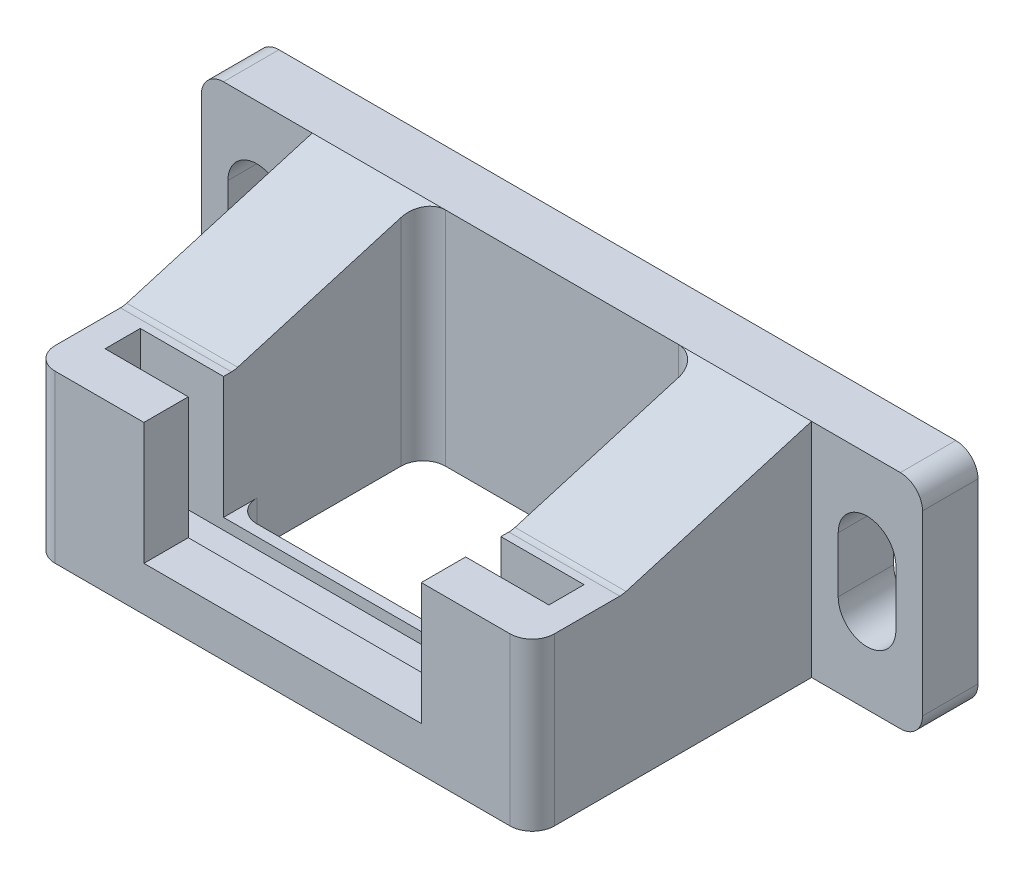
SolidWorks part; units mm, degrees
ref_plane "Front" through (0, 0, 0) normal (0, 0, 1) x (1, 0, 0)
ref_plane "Top" through (0, 0, 0) normal (0, 1, 0) x (1, 0, 0)
ref_plane "Right" through (0, 0, 0) normal (1, 0, 0) x (0, 0, -1)
sketch "Sketch1" plane through (0, 0, 0) normal (1, 0, 0) x (0, 0, -1)
  line L0 (0, 20) -> (0, 0)
  line L1 (0, 0) -> (-30.175, 0)
  line L2 (-30.175, 0) -> (-30.175, 6)
  line L3 (-30.175, 6) -> (-26.175, 6)
  line L4 (-26.175, 6) -> (-26.175, 3)
  line L5 (-26.175, 3) -> (-23, 3)
  line L6 (-23, 3) -> (-23, 6)
  line L7 (-23, 6) -> (-22, 6)
  line L8 (-22, 6) -> (-22, 3)
  line L9 (-22, 3) -> (-5, 3)
  line L10 (-5, 3) -> (-5, 20)
  line L11 (-5, 20) -> (0, 20)
  dimension "D1" = 23
  dimension "D2" = 1
  dimension "D3" = 3.175
  dimension "D4" = 6
  dimension "D5" = 20
  dimension "D7" = 5
  dimension "D8" = 3
  dimension "D9" = 4
extrude "Boss-Extrude1" add sketch "Sketch1" along normal blind 25
ref_plane "Plane1" through (12.5, 0, 0) normal (1, 0, 0) x (0, 0, -1)
sketch "Sketch2" plane through (25, 0, 0) normal (1, 0, 0) x (0, 0, -1)
  line L0 (-30.175, 15) -> (-22, 15)
  line L1 (-22, 15) -> (-5, 20)
  line L2 (-30.175, 6) -> (-30.175, 0) construction
  line L3 (-30.175, 0) -> (0, 0) construction
  line L4 (0, 0) -> (0, 20) construction
  line L5 (0, 20) -> (-5, 20) construction
  line L6 (-30.175, 15) -> (-30.175, 0)
  line L7 (-30.175, 0) -> (0, 0)
  line L8 (0, 0) -> (0, 20)
  line L9 (0, 20) -> (-5, 20)
  line L10 (-22, 15) -> (-22, 6) construction
  dimension "D1" = 5
extrude "Boss-Extrude2" add sketch "Sketch2" along normal blind 10
mirror "Mirror1" about plane through (12.5, 0, 0) normal (1, 0, 0) of "Boss-Extrude2"
sketch "Sketch3" plane through (0, 0, 30.175) normal (0, 0, 1) x (1, 0, 0)
  line L1 (0, 6) -> (25, 6)
  line L2 (0, 6) -> (0, 4)
  line L3 (0, 4) -> (25, 4)
  line L4 (25, 6) -> (25, 4)
  dimension "D1" = 2
extrude "Cut-Extrude1" cut sketch "Sketch3" against normal up to surface (8.175 mm away) up to face at (12.5, 4.5, 22)
sketch "Sketch8" plane through (0, 15, 0) normal (0, 1, 0) x (1, 0, 0)
  line L0 (25, -26.175) -> (0, -26.175) construction
  line L1 (-7.5, -26.175) -> (32.5, -26.175)
  line L2 (-7.5, -26.175) -> (-7.5, -23)
  line L3 (-7.5, -23) -> (32.5, -23)
  line L4 (32.5, -26.175) -> (32.5, -23)
  line L5 (25, -23) -> (0, -23) construction
  line L6 (-7.5, -26.175) -> (-10, -26.175) construction
  line L7 (-10, -22) -> (-10, -30.175) construction
  line L8 (32.5, -26.175) -> (35, -26.175) construction
  line L9 (35, -22) -> (35, -30.175) construction
  dimension "D1" = 2.5
extrude "Cut-Extrude4" cut sketch "Sketch8" against normal up to surface (12 mm away) up to face at (12.5, 3, 24.5875)
sketch "Sketch5" plane through (0, 0, 0) normal (0, -1, 0) x (1, 0, 0)
  line L0 (0, 5) -> (0, 22) construction
  line L1 (0, 5) -> (25, 5)
  line L2 (0, 5) -> (0, 22)
  line L3 (0, 22) -> (25, 22)
  line L4 (25, 5) -> (25, 22)
  line L5 (25, 22) -> (25, 5) construction
  line L8 (35, 0) -> (-10, 0) construction
  dimension "D2" = 5
extrude "Cut-Extrude3" cut sketch "Sketch5" against normal blind 3.175
sketch "Sketch6" plane through (0, 0, 0) normal (0, 0, -1) x (-1, 0, 0)
  line L0 (-40, 20) -> (-40, 0) construction
  line L1 (-35, 20) -> (-45, 20)
  line L2 (-35, 20) -> (-35, 0)
  line L3 (-35, 0) -> (-45, 0)
  line L4 (-45, 20) -> (-45, 0)
  line L5 (-40, 7.5) -> (-40, 12.5) construction
  line L6 (-42.6, 7.5) -> (-42.6, 12.5)
  line L7 (-37.4, 7.5) -> (-37.4, 12.5)
  line L8 (-35, 0) -> (10, 0) construction
  arc A0 (-42.6, 7.5) -> (-37.4, 7.5) centre (-40, 7.5) ccw
  arc A1 (-37.4, 12.5) -> (-42.6, 12.5) centre (-40, 12.5) ccw
  point P9 (-40, 10)
  dimension "D1" = 2.6
  dimension "D2" = 10
  dimension "D3" = 5
extrude "Boss-Extrude3" add sketch "Sketch6" against normal blind 5
fillet "Fillet1" radius 2 8 edges at (-5, 15, 22) (30, 15, 22) (-10, 7.5, 30.175) (35, 7.5, 30.175) (25, 2, 22) (0, 2, 22) (25, 10, 5) (0, 10, 5)
fillet "Fillet2" radius 2 2 edges at (45, 0, 2.5) (45, 20, 2.5)
mirror "Mirror2" about plane through (12.5, 0, 0) normal (1, 0, 0) of "Fillet2", "Boss-Extrude3"
sketch "Sketch9" plane through (-10, 0, 0) normal (-1, 0, 0) x (0, 0, 1)
  line L0 (5, 3) -> (30.175, 3) construction
  line L1 (5, 18) -> (5, 2) construction
  line L2 (30.175, 15) -> (30.175, 0) construction
  line L3 (28.175, 0) -> (5, 0) construction
  text T0 "ZWP-02" font "Century Gothic" height in points 18
  point P6 (0, 0)
  dimension "D1" = 3
extrude "Cut-Extrude5" cut sketch "Sketch9" against normal blind 0.4
